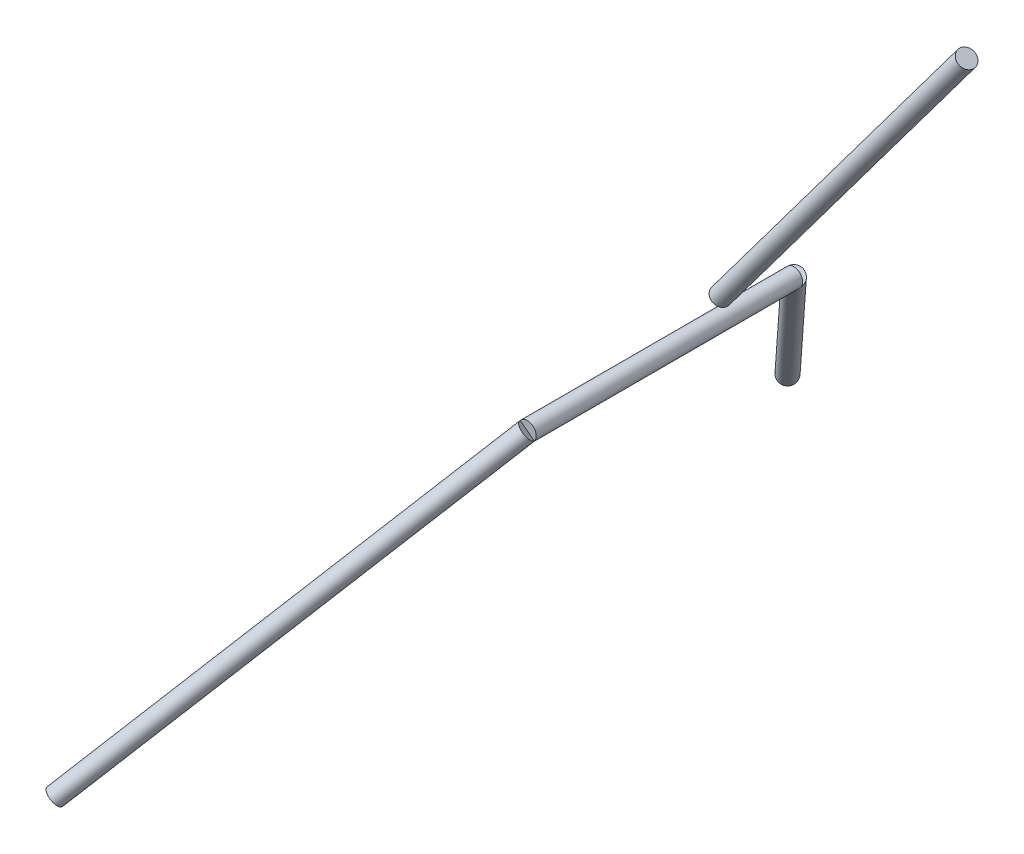
SolidWorks part; units mm, degrees
material "AISI 304"
ref_plane "Alzado" through (0, 0, 0) normal (0, 0, 1) x (1, 0, 0)
ref_plane "Planta" through (0, 0, 0) normal (0, 1, 0) x (1, 0, 0)
ref_plane "Vista lateral" through (0, 0, 0) normal (1, 0, 0) x (0, 0, -1)
sketch3d "Sk_Cable_puente_1"
  line L0 (-219.3921, 374.9527, -33) -> (-197.8236, 403.7762, -12)
  dimension "D1" = 41.6773
sweep "Cable_puente_1" add path "Sk_Cable_puente_1" circular profile diameter 1.6 parameters "D3"=1.6
sketch3d "Sk_Cable_puente_2"
  line L0 (-197.8236, 403.7762, -12) -> (-197.8236, 403.7762, 12)
sweep "Cable_puente_2" add path "Sk_Cable_puente_2" circular profile diameter 1.6 parameters "D3"=1.6
sketch3d "Sk_Cable_puente_3"
  line L0 (-197.8236, 403.7762, 12) -> (-219.3921, 374.9527, 33)
  dimension "D1" = 41.6773
sweep "Cable_puente_3" add path "Sk_Cable_puente_3" circular profile diameter 1.6 parameters "D3"=1.6
sketch3d "Sk_Cable_tiro"
  line L0 (-192.4314, 410.9821, 0) -> (-170.2637, 440.6063, 0)
  dimension "D1" = 37
sweep "Cable_tiro" add path "Sk_Cable_tiro" circular profile diameter 1.6 parameters "D3"=1.6
